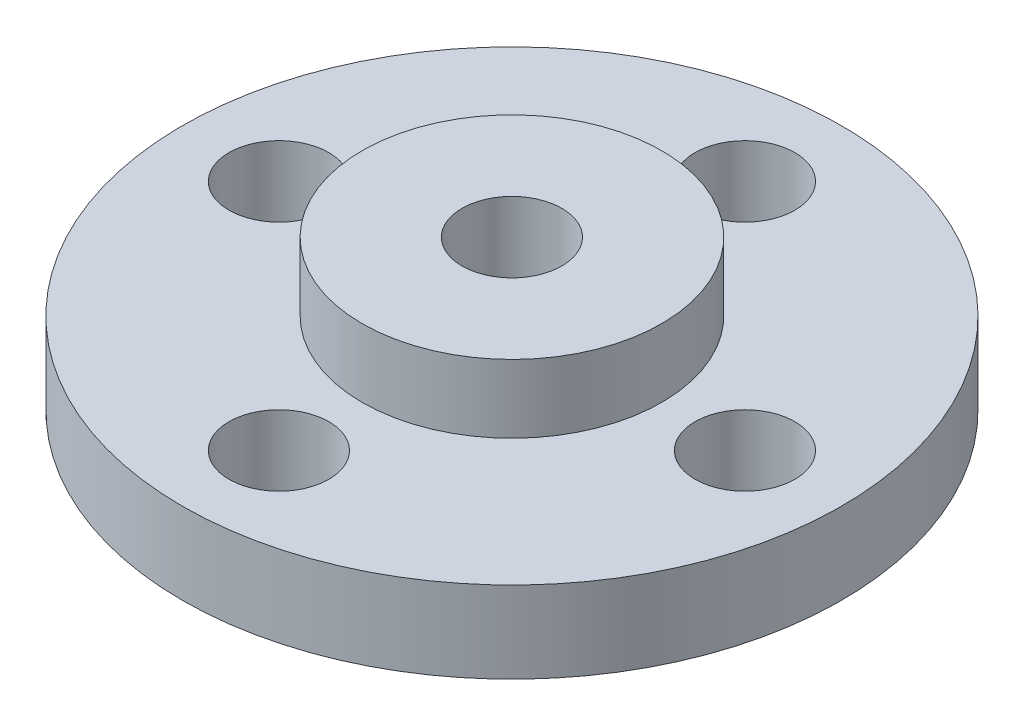
SolidWorks part; units mm, degrees
ref_plane "Front Plane" through (0, 0, 0) normal (0, 0, 1) x (1, 0, 0)
ref_plane "Top Plane" through (0, 0, 0) normal (0, 1, 0) x (1, 0, 0)
ref_plane "Right Plane" through (0, 0, 0) normal (1, 0, 0) x (0, 0, -1)
sketch "Sketch2" plane through (0, 0, 0) normal (0, 1, 0) x (1, 0, 0)
  circle A0 centre (0, 0) radius 9.9
  dimension "D1" = 19.8
extrude "Boss-Extrude2" add sketch "Sketch2" along normal blind 2.45
sketch "Sketch3" plane through (0, 2.45, 0) normal (0, 1, 0) x (1, 0, 0)
  circle A0 centre (0, 0) radius 4.5
  circle A1 centre (0, 0) radius 1.5
  dimension "D1" = 9
  dimension "D2" = 3
extrude "Boss-Extrude3" add sketch "Sketch3" along normal blind 2.05
sketch "Sketch5" plane through (0, 2.45, 0) normal (0, 1, 0) x (1, 0, 0)
  circle A0 centre (0, 0) radius 1.5
extrude "Cut-Extrude1" cut sketch "Sketch5" against normal through all
sketch "Sketch6" plane through (0, 2.45, 0) normal (0, 1, 0) x (1, 0, 0)
  circle A1 centre (7, 0) radius 1.5
  dimension "D1" = 3
extrude "Cut-Extrude2" cut sketch "Sketch6" against normal through all
ref_axis "Axis1" through (0, 4.5, 0) along (0, -1, 0)
pattern_circular "CirPattern1" count 4 over 360 about axis through (0, 4.5, 0) along (0, -1, 0) of "Cut-Extrude2"
